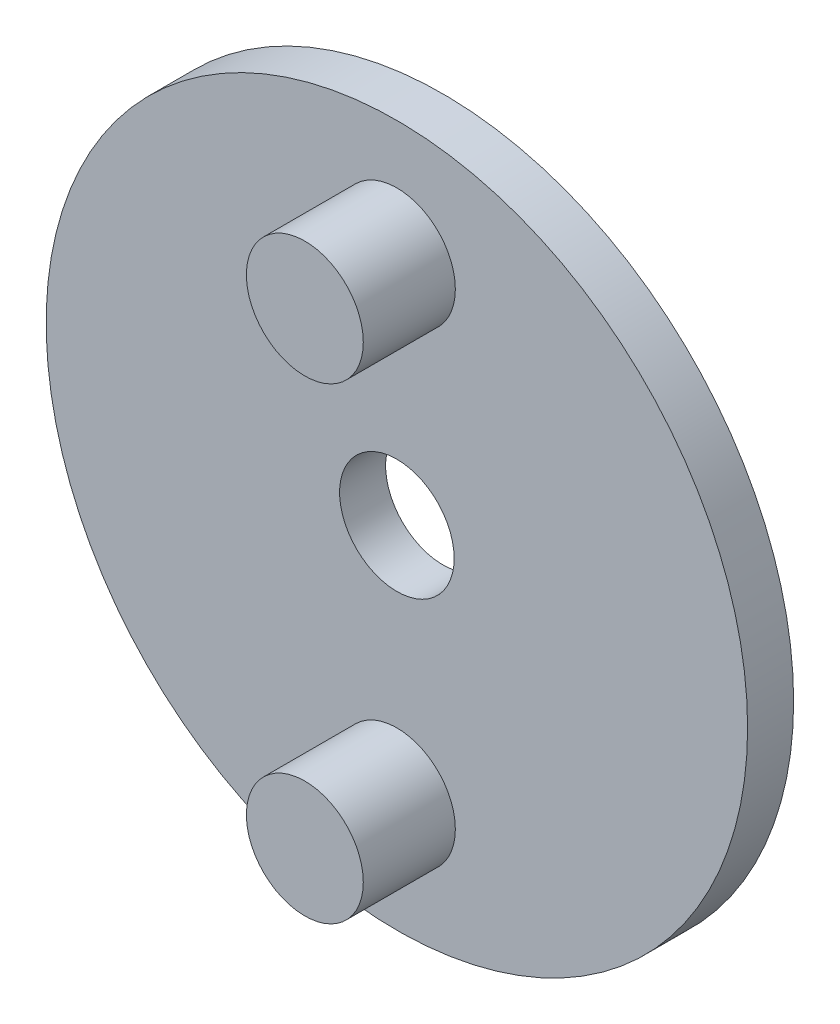
SolidWorks part; units mm, degrees
ref_plane "Front Plane" through (0, 0, 0) normal (0, 0, 1) x (1, 0, 0)
ref_plane "Top Plane" through (0, 0, 0) normal (0, 1, 0) x (1, 0, 0)
ref_plane "Right Plane" through (0, 0, 0) normal (1, 0, 0) x (0, 0, -1)
sketch "Sketch1" plane through (0, 0, 0) normal (0, 0, 1) x (1, 0, 0)
  line L0 (-169.7289, -38.1) -> (169.7289, -38.1) construction
  line L1 (-110.0162, 38.1) -> (110.0162, 38.1) construction
  circle A0 centre (0, 0) radius 38.1
  circle A1 centre (0, 0) radius 6.223
  circle A2 centre (0, -25.4) radius 6.35
  circle A3 centre (0, 25.4) radius 6.35
  point P7 (0, -38.1)
  point P14 (0, 38.1)
  dimension "D1" = 76.2
  dimension "D2" = 12.7
  dimension "D3" = 12.446
  dimension "D5" = 12.7
  dimension "D4" = 12.7
  dimension "D6" = 12.7
extrude "Boss-Extrude1" add sketch "Sketch1" along normal blind 5
sketch "Sketch2" plane through (0, 0, 0) normal (0, 0, 1) x (1, 0, 0)
  circle A0 centre (0, -25.4) radius 6.35
  circle A1 centre (0, 25.4) radius 6.35
  circle A3 centre (0, 25.4) radius 6.35 construction
extrude "Boss-Extrude2" add sketch "Sketch2" along normal blind 15
